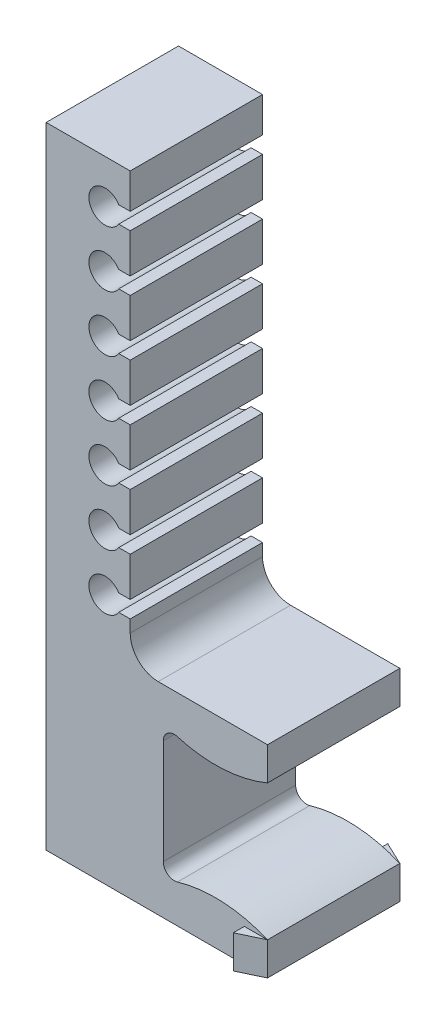
SolidWorks part; units mm, degrees
ref_plane "Front Plane" through (0, 0, 0) normal (0, 0, 1) x (1, 0, 0)
ref_plane "Top Plane" through (0, 0, 0) normal (0, 1, 0) x (1, 0, 0)
ref_plane "Right Plane" through (0, 0, 0) normal (1, 0, 0) x (0, 0, -1)
sketch "Sketch1" plane through (0, 0, 0) normal (0, 0, 1) x (1, 0, 0)
  line L2 (-159.7982, 9.1594) -> (-172.2482, 9.1594)
  line L3 (-172.2482, 9.1594) -> (-172.2482, -9.1594)
  line L7 (-169.2482, -22.8519) -> (-169.2482, 6.1594) construction
  line L13 (-142.8048, 5.1594) -> (-142.8048, -5.1594) construction
  line L23 (-159.7982, 6.1594) -> (-159.7982, 9.1594)
  line L28 (-164.5232, 5.2094) -> (-144.5007, 5.2094) construction
  line L30 (-169.2482, 6.1594) -> (-169.2482, 5.1594)
  line L34 (-169.2482, 5.1594) -> (-169.2482, -5.1594)
  line L35 (-172.2482, 0) -> (-169.2482, 0) construction
  line L36 (-169.2482, -6.1594) -> (-169.2482, -5.1594)
  line L37 (-159.7982, -6.1594) -> (-159.7982, -9.1594)
  line L38 (-159.7982, -9.1594) -> (-172.2482, -9.1594)
  arc A5 (-169.2482, 6.1594) -> (-159.7982, 6.1594) centre (-164.5232, 17.4347) ccw
  arc A6 (-169.2482, -6.1594) -> (-159.7982, -6.1594) centre (-164.5232, -17.4347) cw
  point P30 (-142.8048, 0)
  dimension "D6" = 12.2253
  dimension "D4" = 3
  dimension "D3" = 3
  dimension "D2" = 1
  dimension "D1" = 18.3188
  dimension "D5" = 12.45
extrude "MainBody" add sketch "Sketch1" along normal mid plane 12
sketch "Sketch3" plane through (0, -9.1594, 0) normal (0, -1, 0) x (1, 0, 0)
  line L0 (-159.7982, -6) -> (-161.8982, -7)
  line L1 (-161.8982, -7) -> (-161.8982, -6)
  line L2 (-172.2482, -6) -> (-159.7982, -6) construction
  line L3 (-161.8982, -6) -> (-159.7982, -6)
  line L5 (8.8033, 0) -> (-8.8033, 0) construction
  line L6 (-161.8982, 6) -> (-159.7982, 6)
  line L7 (-161.8982, 7) -> (-161.8982, 6)
  line L8 (-159.7982, 6) -> (-161.8982, 7)
  dimension "D1" = 2.1
  dimension "D2" = 1
extrude "Hook" add sketch "Sketch3" against normal up to vertex (3 mm away) up to point (-159.7982, -6.1594, -6)
fillet "Fillet2" radius 1 2 edges at (-169.2482, 6.1594, 0) (-169.2482, -6.1594, 0)
sketch "Sketch5" [suppressed] plane through (-172.2482, 0, 0) normal (-1, 0, 0) x (0, 0, 1)
  line L1 (-6, 9.1594) -> (6, 9.1594)
  line L2 (-6, 9.1594) -> (-6, -9.1594)
  line L3 (-6, -9.1594) -> (6, -9.1594)
  line L4 (6, 9.1594) -> (6, -9.1594)
extrude "Boss-Extrude1" [suppressed] add sketch "Sketch5" along normal blind 15
sketch "Sketch6" [suppressed] plane through (0, 9.1594, 0) normal (0, 1, 0) x (1, 0, 0)
  line L0 (-187.2482, -6) -> (-187.2482, 6) construction
  circle A0 centre (-182.2482, 0) radius 3.302
  dimension "D1" = 6.604
  dimension "D2" = 5
extrude "Cut-Extrude2" [suppressed] cut sketch "Sketch6" against normal through all
sketch "Sketch7" [suppressed] plane through (-172.2482, 0, 0) normal (-1, 0, 0) x (0, 0, 1)
  circle A0 centre (0, 0) radius 38.1
  dimension "D1" = 76.2
extrude "Boss-Extrude2" [suppressed] add sketch "Sketch7" along normal blind 5
fillet "Fillet3" [suppressed] radius 1
sketch "Sketch8" [suppressed] plane through (0, 0, 6) normal (0, 0, 1) x (1, 0, 0)
  line L6 (-172.2482, -0.635) -> (-173.4343, -0.635)
  line L8 (-172.2482, 0.635) -> (-173.4343, 0.635)
  line L10 (-172.2482, 0.635) -> (-173.4343, 0.635)
  line L11 (-172.2482, 0.635) -> (-172.2482, -0.635)
  line L12 (-159.7982, -9.1594) -> (-159.7982, -6.1594)
  line L13 (-159.7982, -9.1594) -> (-159.7982, -6.1594)
  line L14 (-169.2482, -6.1594) -> (-169.2482, 6.1594)
  line L15 (-159.7982, 6.1594) -> (-159.7982, 9.1594)
  line L16 (-159.7982, 9.1594) -> (-172.2482, 9.1594)
  line L17 (-172.2482, 9.1594) -> (-172.2482, -9.1594)
  line L18 (-172.2482, -9.1594) -> (-159.7982, -9.1594)
  line L21 (-169.2482, -6.1594) -> (-169.2482, 6.1594)
  line L22 (-159.7982, 6.1594) -> (-159.7982, 9.1594)
  line L23 (-159.7982, 9.1594) -> (-172.2482, 9.1594)
  line L24 (-172.2482, 9.1594) -> (-172.2482, -9.1594)
  line L25 (-172.2482, -9.1594) -> (-159.7982, -9.1594)
  line L26 (-172.2482, -0.635) -> (-173.4343, -0.635)
  arc A0 (-173.4343, 0.635) -> (-173.4343, -0.635) centre (-174.5342, 0) ccw
  arc A4 (-159.7982, -6.1594) -> (-169.2482, -6.1594) centre (-164.5232, -17.4347) ccw
  arc A7 (-169.2482, 6.1594) -> (-159.7982, 6.1594) centre (-164.5232, 17.4347) ccw
  arc A8 (-159.7982, -6.1594) -> (-169.2482, -6.1594) centre (-164.5232, -17.4347) ccw
  arc A11 (-169.2482, 6.1594) -> (-159.7982, 6.1594) centre (-164.5232, 17.4347) ccw
  point P6 (-172.2482, 0)
  line M14 (-172.2482, 9.1594) -> (-172.2482, -9.1594)
  dimension "D2" = 1.27
  dimension "D1" = 0
  dimension "D3" = 2.286
extrude "Slot" [suppressed] add sketch "Sketch8" against normal up to surface (12 mm away) contours L8 A0 L6 M14 up to face at (-165.6835, -0.5599, -6)
sketch "Sketch10" [suppressed] plane through (0, 0, -6) normal (0, 0, -1) x (-1, 0, 0)
  line L0 (166.0232, -9.1594) -> (172.2482, -9.1594)
  line L3 (172.2482, -9.1594) -> (166.0232, -9.1594)
  line L5 (172.2482, -9.1594) -> (187.9767, -44.4861)
  line L6 (195.4932, -61.3685) -> (192.3182, -61.3685)
  line L7 (159.7982, -6.1594) -> (159.7982, -9.1594)
  line L8 (159.7982, -6.1594) -> (159.7982, -9.1594)
  line L9 (159.7982, -9.1594) -> (172.2482, -9.1594)
  line L10 (172.2482, -9.1594) -> (172.2482, 9.1594)
  line L11 (172.2482, 9.1594) -> (159.7982, 9.1594)
  line L12 (159.7982, 9.1594) -> (159.7982, 6.1594)
  line L13 (169.2482, 6.1594) -> (169.2482, -6.1594)
  line L16 (159.7982, -9.1594) -> (172.2482, -9.1594)
  line L17 (172.2482, -9.1594) -> (172.2482, 9.1594)
  line L18 (172.2482, 9.1594) -> (159.7982, 9.1594)
  line L19 (159.7982, 9.1594) -> (159.7982, 6.1594)
  line L20 (169.2482, 6.1594) -> (169.2482, -6.1594)
  line L21 (195.4932, -61.3685) -> (201.8432, -61.3685)
  line L22 (201.8432, -61.3685) -> (201.8432, -59.781)
  line L24 (192.666, -55.0185) -> (200.9772, -55.0185)
  line L25 (169.0732, -9.1594) -> (192.3182, -61.3685)
  line L28 (201.8432, -59.781) -> (194.7864, -59.781)
  line L31 (193.3728, -56.606) -> (200.9772, -56.606)
  line L42 (200.9772, -55.0185) -> (200.9772, -56.606)
  line L43 (187.9767, -44.4861) -> (195.4932, -61.3685)
  arc A4 (169.2482, -6.1594) -> (159.7982, -6.1594) centre (164.5232, -17.4347) ccw
  arc A5 (159.7982, 6.1594) -> (169.2482, 6.1594) centre (164.5232, 17.4347) ccw
  arc A8 (169.2482, -6.1594) -> (159.7982, -6.1594) centre (164.5232, -17.4347) ccw
  arc A9 (159.7982, 6.1594) -> (169.2482, 6.1594) centre (164.5232, 17.4347) ccw
  dimension "D5" = 6.35
  dimension "D7" = 3.175
  dimension "D8" = 3.175
  dimension "D2" = 57.15
  dimension "D10" = 1.5875
  dimension "D13" = 114
  dimension "D14" = 114
  dimension "D3" = 1.5875
  dimension "D4" = 3.175
extrude "Boss-Extrude3" [suppressed] add sketch "Sketch10" against normal up to surface (12 mm away) up to face at (-165.6835, -0.5599, 6)
sketch "Sketch11" [suppressed] plane through (0, 0, -6) normal (0, 0, -1) x (-1, 0, 0)
  line L0 (159.7982, -9.1594) -> (159.7982, 9.1594)
  line L11 (169.2482, 6.1594) -> (169.2482, -6.1594)
  line L12 (159.7982, -6.1594) -> (159.7982, -9.1594)
  line L13 (159.7982, -9.1594) -> (169.0732, -9.1594)
  line L14 (169.0732, -9.1594) -> (192.3182, -61.3685)
  line L15 (192.3182, -61.3685) -> (201.8432, -61.3685)
  line L16 (201.8432, -61.3685) -> (201.8432, -59.781)
  line L17 (201.8432, -59.781) -> (194.7864, -59.781)
  line L18 (194.7864, -59.781) -> (193.3728, -56.606)
  line L19 (172.2482, -9.1594) -> (172.2482, 9.1594)
  line L20 (172.2482, 9.1594) -> (159.7982, 9.1594)
  line L21 (159.7982, 9.1594) -> (159.7982, 6.1594)
  line L22 (169.2482, 6.1594) -> (169.2482, -6.1594)
  line L23 (159.7982, -6.1594) -> (159.7982, -9.1594)
  line L24 (159.7982, -9.1594) -> (169.0732, -9.1594)
  line L25 (169.0732, -9.1594) -> (192.3182, -61.3685)
  line L26 (192.3182, -61.3685) -> (201.8432, -61.3685)
  line L27 (201.8432, -61.3685) -> (201.8432, -59.781)
  line L28 (201.8432, -59.781) -> (194.7864, -59.781)
  line L29 (194.7864, -59.781) -> (193.3728, -56.606)
  line L30 (172.2482, -9.1594) -> (172.2482, 9.1594)
  line L31 (172.2482, 9.1594) -> (159.7982, 9.1594)
  line L32 (159.7982, 9.1594) -> (159.7982, 6.1594)
  line L37 (193.3728, -56.606) -> (200.9772, -56.606)
  line L38 (193.3728, -56.606) -> (200.9772, -56.606)
  line L39 (200.9772, -56.606) -> (200.9772, -55.0185)
  line L40 (200.9772, -56.606) -> (200.9772, -55.0185)
  line L41 (192.666, -55.0185) -> (172.2482, -9.1594)
  line L42 (192.666, -55.0185) -> (172.2482, -9.1594)
  line L44 (200.9772, -55.0185) -> (192.666, -55.0185)
  line L45 (200.9772, -55.0185) -> (192.666, -55.0185)
  arc A2 (159.7982, 6.1594) -> (169.2482, 6.1594) centre (164.5232, 17.4347) ccw
  arc A3 (169.2482, -6.1594) -> (159.7982, -6.1594) centre (164.5232, -17.4347) ccw
  arc A4 (159.7982, 6.1594) -> (169.2482, 6.1594) centre (164.5232, 17.4347) ccw
  arc A5 (169.2482, -6.1594) -> (159.7982, -6.1594) centre (164.5232, -17.4347) ccw
  arc M14 (159.7982, 6.1594) -> (169.2482, 6.1594) centre (164.5232, 17.4347) ccw
  line M15 (169.2482, 6.1594) -> (169.2482, -6.1594)
  arc M16 (169.2482, -6.1594) -> (159.7982, -6.1594) centre (164.5232, -17.4347) ccw
  dimension "D1" = 0
extrude "Boss-Extrude4" [suppressed] add sketch "Sketch11" against normal up to surface (12 mm away) contours L0 M16 M15 M14 up to face at (-165.6835, -0.5599, 6)
sketch "Sketch12" [suppressed] plane through (0, 0, -6) normal (0, 0, -1) x (-1, 0, 0)
  line L0 (159.7982, -9.1594) -> (159.7982, -5.9844)
  line L1 (159.7982, -5.9844) -> (162.0842, -5.9844)
  line L3 (162.0842, -5.2351) -> (159.7982, -5.2351)
  line L4 (162.0842, -5.2351) -> (162.0842, -6.7337)
  line L5 (162.0842, -6.7337) -> (159.7982, -6.7337)
  line L6 (159.7982, -5.2351) -> (159.7982, -6.7337)
  line L7 (162.0842, -5.2351) -> (159.7982, -6.7337) construction
  line L8 (162.0842, -6.7337) -> (159.7982, -5.2351) construction
  line L9 (172.2482, 9.1594) -> (159.7982, 9.1594)
  line L10 (159.7982, 9.1594) -> (159.7982, -9.1594)
  line L11 (159.7982, -9.1594) -> (169.0732, -9.1594)
  line L12 (169.0732, -9.1594) -> (192.3182, -61.3685)
  line L13 (192.3182, -61.3685) -> (201.8432, -61.3685)
  line L14 (201.8432, -61.3685) -> (201.8432, -59.781)
  line L15 (201.8432, -59.781) -> (194.7864, -59.781)
  line L16 (194.7864, -59.781) -> (193.3728, -56.606)
  line L17 (172.2482, -9.1594) -> (172.2482, 9.1594)
  line L18 (172.2482, 9.1594) -> (159.7982, 9.1594)
  line L19 (159.7982, 9.1594) -> (159.7982, -9.1594)
  line L20 (159.7982, -9.1594) -> (169.0732, -9.1594)
  line L21 (169.0732, -9.1594) -> (192.3182, -61.3685)
  line L22 (192.3182, -61.3685) -> (201.8432, -61.3685)
  line L23 (201.8432, -61.3685) -> (201.8432, -59.781)
  line L24 (201.8432, -59.781) -> (194.7864, -59.781)
  line L25 (194.7864, -59.781) -> (193.3728, -56.606)
  line L26 (172.2482, -9.1594) -> (172.2482, 9.1594)
  line L38 (193.3728, -56.606) -> (200.9772, -56.606)
  line L39 (193.3728, -56.606) -> (200.9772, -56.606)
  line L40 (200.9772, -56.606) -> (200.9772, -55.0185)
  line L42 (192.666, -55.0185) -> (172.2482, -9.1594)
  line L43 (192.666, -55.0185) -> (172.2482, -9.1594)
  line L45 (200.9772, -56.606) -> (200.9772, -55.0185)
  line L46 (200.9772, -55.0185) -> (192.666, -55.0185)
  line L47 (200.9772, -55.0185) -> (192.666, -55.0185)
  circle A0 centre (162.0842, -5.9844) radius 1.3843
  point P8 (160.9412, -5.9844)
  line M13 (159.7982, 9.1594) -> (159.7982, -9.1594)
  dimension "D4" = 2.7686
  dimension "D2" = 3.175
  dimension "D3" = 2.286
  dimension "D5" = 1.4986
extrude "Cut-Extrude3" [suppressed] cut sketch "Sketch12" against normal up to surface (12 mm away) contours L5 A0 L3 L4 | L1 A0 L5 L4 | A0 L1 L5 M13 | L3 A0 L1 L4 | A0 L3 L1 M13 up to face at (-165.6835, -0.5599, 6)
pattern_linear "LPattern1" [suppressed] count 4 spacing 4.28 of bodies 117
sketch "Sketch15" plane through (0, 0, 6) normal (0, 0, 1) x (1, 0, 0)
  line L1 (-172.2482, -9.1594) -> (-179.8682, -9.1594)
  line L2 (-172.2482, -9.1594) -> (-172.2482, 47.9906)
  line L3 (-172.2482, 47.9906) -> (-179.8682, 47.9906)
  line L4 (-179.8682, -9.1594) -> (-179.8682, 47.9906)
  dimension "D1" = 7.62
  dimension "D2" = 57.15
extrude "Boss-Extrude6" add sketch "Sketch15" against normal up to surface (12 mm away) up to face at (-165.6835, -0.5599, -6)
sketch "Sketch16" plane through (0, 0, 6) normal (0, 0, 1) x (1, 0, 0)
  line L0 (-172.2482, 9.1594) -> (-172.2482, 47.9906) construction
  line L1 (-172.2482, 44.8156) -> (-174.5342, 44.8156)
  line L2 (-172.2482, 44.8156) -> (-172.2482, 43.2916)
  line L3 (-172.2482, 43.2916) -> (-174.5342, 43.2916)
  line L4 (-174.5342, 44.8156) -> (-174.5342, 43.2916)
  line L5 (-172.2482, 47.9906) -> (-179.8682, 47.9906) construction
  circle A0 centre (-174.5342, 44.0536) radius 1.4605
  line M12 (-172.2482, 9.1594) -> (-172.2482, 47.9906)
  dimension "D4" = 2.921
  dimension "D1" = 3.175
  dimension "D2" = 1.524
  dimension "D3" = 2.286
extrude "Cut-Extrude6" cut sketch "Sketch16" against normal up to surface (12 mm away) contours A0 L3 L1 M12 | L3 A0 L1 L4 | L1 A0 L3 L4 region at (-172.6978, 44.0536, 6) region at (-173.8371, 44.0536, 6) region at (-174.8568, 44.0536, 6) up to face at (-167.8658, 6.9094, -6)
pattern_linear "LPattern3" count 7 spacing 5.08 along (0, -1, 0) of "Cut-Extrude6"
fillet "Fillet5" radius 2.54 1 edges at (-172.2482, 9.1594, 0)
equation "\"HookThickness\"= 3mm"
equation "\"D3@Sketch1\"=\"HookThickness\""
equation "\"D4@Sketch1\"=\"HookThickness\""
equation "\"CylinderDiameter\"=3"
equation "\"D1@Sketch7\"=\"CylinderDiameter\""
equation "\"Mount Tolerance\"= .005in"
equation "\"Mount Thickness\"= .0625in"
equation "\"Mount Angle\"= 114"
equation "\"D14@Sketch10\"=\"Mount Angle\""
equation "\"D13@Sketch10\"= \"Mount Angle\""
equation "\"Joint Radius\"= .05in"
equation "\"Joint Thickness\"= .05in"
equation "\"Joint Tolerance\"= .009in"
equation "\"D4@Sketch12\"= (\"Joint Radius\" * 2) + \"Joint Tolerance\""
equation "\"D5@Sketch12\"= \"Joint Thickness\" + \"Joint Tolerance\""
